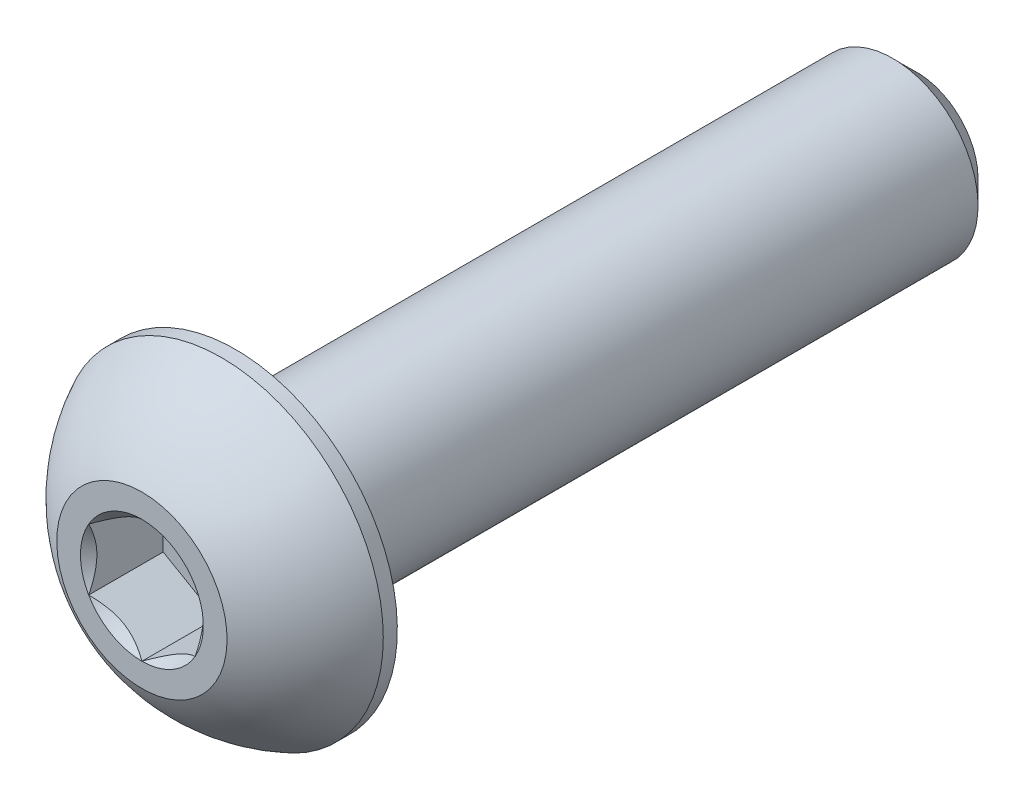
SolidWorks part; units mm, degrees
ref_plane "Front Plane" through (0, 0, 0) normal (0, 0, 1) x (1, 0, 0)
ref_plane "Top Plane" through (0, 0, 0) normal (0, 1, 0) x (1, 0, 0)
ref_plane "Right Plane" through (0, 0, 0) normal (1, 0, 0) x (0, 0, -1)
sketch "Sketch1" plane through (0, 0, 0) normal (1, 0, 0) x (0, 0, -1)
  line L0 (-9.1, 0) -> (9.1, 0) construction
  line L1 (-6.9, 3.8) -> (-6.9, -3.8) construction
  line L2 (9.1, 2) -> (9.1, -2) construction
  line L3 (9.0563, 2.0758) -> (9.4063, 1.4696) construction
  line L4 (9.4063, 1.4696) -> (9.7563, 2.0758) construction
  line L5 (9.7563, 2.0758) -> (9.0563, 2.0758) construction
  line L6 (9.1, 2) -> (9.7125, 2) construction
  line L7 (9.4063, 2.0758) -> (9.4063, 2) construction
  line L8 (9.4063, 2) -> (9.4063, 1.5453) construction
  line L9 (9.4063, 1.5453) -> (9.4063, 1.4696) construction
  line L10 (9.3625, 1.5453) -> (9.45, 1.5453)
  line L11 (9.0781, 2.0379) -> (9.7344, 2.0379)
  line L12 (9.45, 1.5453) -> (9.7344, 2.0379)
  line L13 (9.3625, 1.5453) -> (9.0781, 2.0379)
  line L14 (-9.1, 1.25) -> (-9.1, -1.25) construction
  line L15 (9.1, 2) -> (-6.9, 2) construction
  point P3 (-6.9, 0)
  point P6 (-7.35, 0)
  point P21 (9.4063, 2.0379)
  point P24 (-7.23, 3.8)
  point P25 (7.35, -2)
  point P26 (-9.1, 2)
  dimension "Head Height" = 2.2
  dimension "Length" = 16
  dimension "Head Dia" = 7.6
  dimension "Thread Dia" = 4
  dimension "Pitch" = 0.7
  dimension "D2" = 0.0875
  dimension "Drive Size" = 2.5
  dimension "D1" = 1.75
  dimension "D3" = 0.33
  dimension "D4" = 1.75
sketch "Sketch2" plane through (0, 0, 0) normal (1, 0, 0) x (0, 0, -1)
  line L0 (-9.1, 0) -> (9.1, 0)
  line L1 (9.1, 0) -> (9.1, 1.44)
  line L2 (9.1, 2) -> (9.1, -2) construction
  line L3 (9.1, 1.44) -> (8.54, 2)
  line L4 (8.54, 2) -> (-6.9, 2)
  line L5 (-6.9, 3.8) -> (-6.9, -3.8) construction
  line L6 (-6.9, 2) -> (-6.9, 3.8)
  line L7 (-6.9, 3.8) -> (-7.23, 3.8)
  line L8 (9.1, 2) -> (9.7125, 2) construction
  line L9 (-9.1, 0) -> (-9.1, 2)
  arc A0 (-9.1, 2) -> (-7.23, 3.8) centre (-5.3736, 0) cw
  dimension "D1" = 0.56
  dimension "D2" = 45
revolve "Revolve1" add sketch "Sketch2" angle 360 about L0
sketch "Sketch3" plane through (0, 0, 9.1) normal (0, 0, 1) x (1, 0, 0)
  line L1 (0, 1.4434) -> (-1.25, 0.7217)
  line L2 (-1.25, 0.7217) -> (-1.25, -0.7217)
  line L3 (-1.25, -0.7217) -> (0, -1.4434)
  line L4 (0, -1.4434) -> (1.25, -0.7217)
  line L5 (1.25, -0.7217) -> (1.25, 0.7217)
  line L6 (1.25, 0.7217) -> (0, 1.4434)
  circle A0 centre (0, 0) radius 1.25 construction
  dimension "D1" = 2.5
extrude "Cut-Extrude1" cut sketch "Sketch3" against normal up to vertex (1.75 mm away) up to point (0, 0, 7.35)
sketch "Sketch4" plane through (0, 0, 9.1) normal (0, 0, 1) x (1, 0, 0)
  circle A0 centre (0, 0) radius 1.4434
extrude "Cut-Extrude2" cut sketch "Sketch4" against normal blind 10 draft 45
split "Split1" [suppressed] bodies to split 106
sketch "Sketch5" [suppressed] plane through (0, 0, -9.1) normal (0, 0, -1) x (-1, 0, 0)
  circle A0 centre (0, 0) radius 2 construction
  circle A1 centre (0, 0) radius 2
curve "Helix/Spiral1" [suppressed] pitch 0.7 height 16.7 turns 23.8571
sketch "Sketch6" [suppressed] plane through (0, 0, 0) normal (1, 0, 0) x (0, 0, -1)
  line L0 (9.3625, 1.5453) -> (9.45, 1.5453) construction
  line L1 (9.3625, 1.5453) -> (9.0781, 2.0379) construction
  line L2 (9.0781, 2.0379) -> (9.7344, 2.0379) construction
  line L3 (9.45, 1.5453) -> (9.7344, 2.0379) construction
  line L4 (9.3625, 1.5453) -> (9.45, 1.5453)
  line L5 (9.3625, 1.5453) -> (9.0781, 2.0379)
  line L6 (9.0781, 2.0379) -> (9.7344, 2.0379)
  line L7 (9.45, 1.5453) -> (9.7344, 2.0379)
sweep "Cut-Sweep1" [suppressed] cut profiles "Sketch6" path "Helix/Spiral1"
sketch "Sketch7" [suppressed] plane through (0, 0, 6.9) normal (0, 0, -1) x (-1, 0, 0)
  circle A1 centre (0, 0) radius 2
  circle A2 centre (0, 0) radius 2
  dimension "D1" = 0
extrude "Boss-Extrude1" [suppressed] add sketch "Sketch7" along normal blind 10 draft 30
equation "\"D2@Sketch1\" = \"Pitch@Sketch1\" / 8"
equation "\"D1@Sketch1\"=\"Drive Size@Sketch1\"*.7"
equation "\"D3@Sketch1\"=\"Head Height@Sketch1\"*.15"
equation "\"D1@Sketch2\"=\"Pitch@Sketch1\"*.8"
equation "\"D1@Sketch3\"=\"Drive Size@Sketch1\""
equation "\"D4@Helix/Spiral1\"=\"Pitch@Sketch1\""
equation "\"D3@Helix/Spiral1\"=\"Length@Sketch1\"+\"Pitch@Sketch1\""
equation "\"D4@Sketch1\"=\"Pitch@Sketch1\"*2.5"
